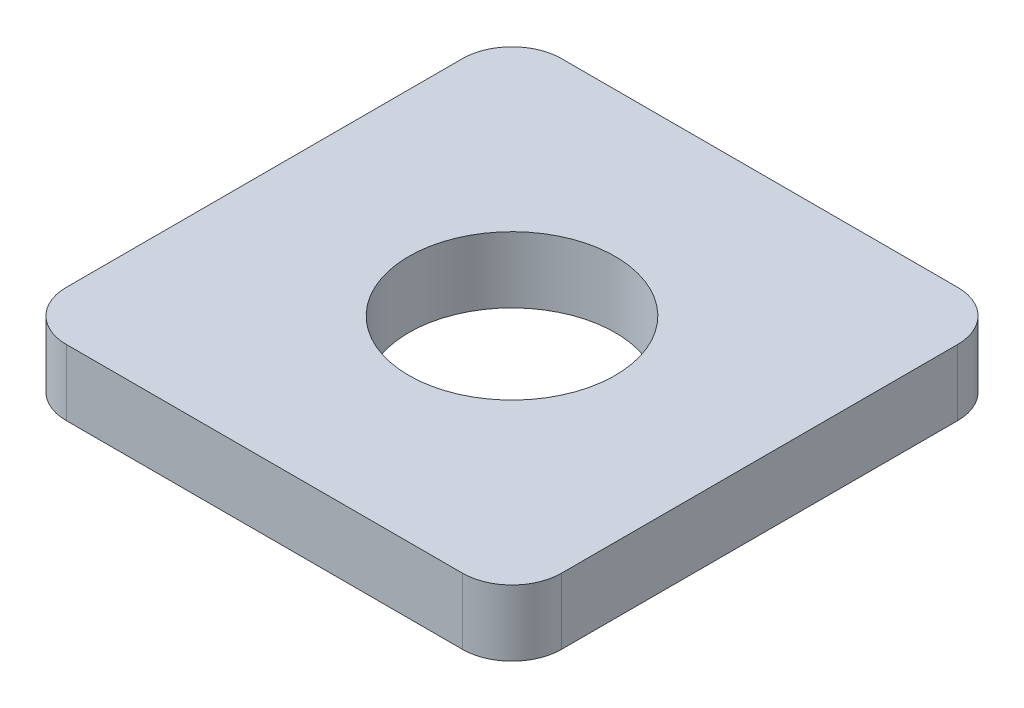
SolidWorks part; units mm, degrees
material "СТ3КП"
ref_plane "Спереди" through (0, 0, 0) normal (0, 0, 1) x (1, 0, 0)
ref_plane "Сверху" through (0, 0, 0) normal (0, 1, 0) x (1, 0, 0)
ref_plane "Справа" through (0, 0, 0) normal (1, 0, 0) x (0, 0, -1)
sketch "Эскиз1" plane through (0, 0, 0) normal (0, 1, 0) x (1, 0, 0)
  line L0 (12, 15) -> (-12, 15) construction
  line L1 (15, -12) -> (15, 12) construction
  line L2 (-12, -15) -> (12, -15) construction
  line L3 (-15, 12) -> (-15, -12) construction
  line L4 (12, 15) -> (-12, 15)
  line L5 (15, -12) -> (15, 12)
  line L6 (-12, -15) -> (12, -15)
  line L7 (-15, 12) -> (-15, -12)
  arc A0 (-12, 15) -> (-15, 12) centre (-12, 12) ccw construction
  arc A1 (15, 12) -> (12, 15) centre (12, 12) ccw construction
  arc A2 (12, -15) -> (15, -12) centre (12, -12) ccw construction
  arc A3 (-15, -12) -> (-12, -15) centre (-12, -12) ccw construction
  arc A4 (-12, 15) -> (-15, 12) centre (-12, 12) ccw
  arc A5 (15, 12) -> (12, 15) centre (12, 12) ccw
  arc A6 (12, -15) -> (15, -12) centre (12, -12) ccw
  arc A7 (-15, -12) -> (-12, -15) centre (-12, -12) ccw
  circle A8 centre (0, 0) radius 6.25
  dimension "D1" = 12.5
base flange "Базовая кромка1" sketch "Эскиз1" thickness 4 reverse thickness direction no parameters "D1"=1.5
sketch "Сгиб-Линии1" plane through (0, 0, 0) normal (0, 1, 0) x (1, 0, 0)
sketch "Граничная рамка1" plane through (0, 0, 0) normal (0, 1, 0) x (1, 0, 0)
sheet metal parameters "Листовой металл3" thickness 4 parameters "D1"=1.5
flat pattern "Развертка3" [suppressed]
sketch "Сгиб-Линии2" plane through (0, 0, 0) normal (0, 1, 0) x (1, 0, 0)
sketch "Граничная рамка2" [suppressed] plane through (0, 0, 0) normal (0, 1, 0) x (1, 0, 0)
